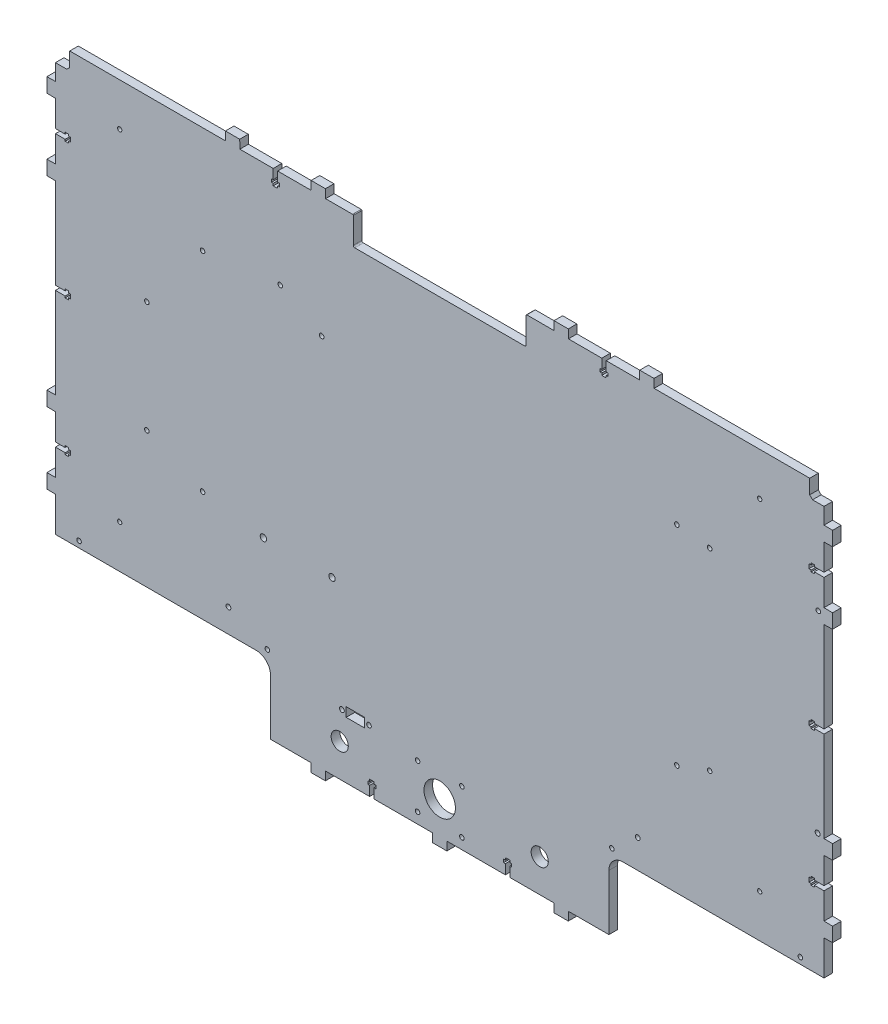
SolidWorks part; units mm, degrees
material "Клен"
ref_plane "Front" through (0, 0, 0) normal (0, 0, 1) x (1, 0, 0)
ref_plane "Top" through (0, 0, 0) normal (0, 1, 0) x (1, 0, 0)
ref_plane "Right" through (0, 0, 0) normal (1, 0, 0) x (0, 0, -1)
sketch "Эскиз1" plane through (0, 0, 0) normal (0, 0, 1) x (1, 0, 0)
  line L0 (89.7419, 500.1376) -> (118.0919, 500.1376)
  line L1 (118.0919, 500.1376) -> (118.1919, 494.1376)
  line L2 (118.1919, 494.1376) -> (128.1919, 494.1376)
  line L3 (128.1919, 494.1376) -> (128.2919, 500.1376)
  line L4 (128.2919, 500.1376) -> (159.1419, 500.1376)
  line L5 (159.1419, 500.1376) -> (159.1419, 506.9376)
  line L6 (159.1419, 506.9376) -> (157.9419, 506.9376)
  line L7 (157.9419, 506.9376) -> (157.9419, 509.1376)
  line L8 (157.9419, 509.1376) -> (159.1419, 509.1376)
  line L9 (159.1419, 509.1376) -> (159.1419, 510.6376)
  line L10 (159.1419, 510.6376) -> (162.2419, 510.6376)
  line L11 (162.2419, 510.6376) -> (162.2419, 509.1376)
  line L12 (162.2419, 509.1376) -> (163.4419, 509.1376)
  line L13 (163.4419, 509.1376) -> (163.4419, 506.9376)
  line L14 (163.4419, 506.9376) -> (162.2419, 506.9376)
  line L15 (162.2419, 506.9376) -> (162.2419, 500.1376)
  line L16 (-51.8081, 695.792) -> (-54.0081, 695.792)
  line L17 (-66.8081, 623.542) -> (-60.8081, 623.442)
  line L18 (162.2419, 500.1376) -> (203.0919, 500.1376)
  line L19 (203.0919, 500.1376) -> (203.1919, 494.1376)
  line L20 (203.1919, 494.1376) -> (213.1919, 494.1376)
  line L21 (213.1919, 494.1376) -> (213.2919, 500.1376)
  line L22 (213.2919, 500.1376) -> (254.1419, 500.1376)
  line L23 (254.1419, 500.1376) -> (254.1419, 506.9376)
  line L24 (254.1419, 506.9376) -> (252.9419, 506.9376)
  line L25 (252.9419, 506.9376) -> (252.9419, 509.1376)
  line L26 (252.9419, 509.1376) -> (254.1419, 509.1376)
  line L27 (254.1419, 509.1376) -> (254.1419, 510.6376)
  line L28 (254.1419, 510.6376) -> (257.2419, 510.6376)
  line L29 (257.2419, 510.6376) -> (257.2419, 509.1376)
  line L30 (257.2419, 509.1376) -> (258.4419, 509.1376)
  line L31 (258.4419, 509.1376) -> (258.4419, 506.9376)
  line L32 (258.4419, 506.9376) -> (257.2419, 506.9376)
  line L33 (257.2419, 506.9376) -> (257.2419, 500.1376)
  line L34 (257.2419, 500.1376) -> (288.0919, 500.1376)
  line L35 (288.0919, 500.1376) -> (288.1919, 494.1376)
  line L36 (288.1919, 494.1376) -> (298.1919, 494.1376)
  line L37 (298.1919, 494.1376) -> (298.2919, 500.1376)
  line L38 (298.2919, 500.1376) -> (326.6419, 500.1376)
  line L97 (367.1919, 847.1376) -> (358.2919, 847.1376)
  line L98 (358.2919, 847.1376) -> (358.1919, 853.1376)
  line L99 (358.1919, 853.1376) -> (348.1919, 853.1376)
  line L100 (348.1919, 853.1376) -> (348.0919, 847.1376)
  line L101 (348.0919, 847.1376) -> (324.7419, 847.1376)
  line L102 (324.7419, 847.1376) -> (324.7419, 840.3376)
  line L103 (324.7419, 840.3376) -> (325.9419, 840.3376)
  line L104 (325.9419, 840.3376) -> (325.9419, 838.1376)
  line L105 (325.9419, 838.1376) -> (324.7419, 838.1376)
  line L106 (324.7419, 838.1376) -> (324.7419, 836.6376)
  line L107 (324.7419, 836.6376) -> (321.6419, 836.6376)
  line L108 (321.6419, 836.6376) -> (321.6419, 838.1376)
  line L109 (321.6419, 838.1376) -> (320.4419, 838.1376)
  line L110 (320.4419, 838.1376) -> (320.4419, 840.3376)
  line L111 (320.4419, 840.3376) -> (321.6419, 840.3376)
  line L112 (321.6419, 840.3376) -> (321.6419, 847.1376)
  line L113 (321.6419, 847.1376) -> (298.2919, 847.1376)
  line L114 (298.2919, 847.1376) -> (298.1919, 853.1376)
  line L115 (298.1919, 853.1376) -> (288.1919, 853.1376)
  line L116 (288.1919, 853.1376) -> (288.0919, 847.1376)
  line L117 (288.0919, 847.1376) -> (269.1919, 847.1376)
  line L118 (268.6919, 846.6376) -> (268.6919, 828.542)
  line L119 (267.6919, 827.542) -> (148.6919, 827.542)
  line L120 (147.6919, 828.542) -> (147.6919, 846.542)
  line L130 (94.7419, 838.042) -> (94.7419, 836.542)
  line L131 (94.7419, 836.542) -> (91.6419, 836.542)
  line L132 (91.6419, 836.542) -> (91.6419, 838.042)
  line L199 (39.1919, 871.432) -> (39.1919, 501.6876) construction
  line L201 (142.7002, 546.3976) -> (155.7002, 546.3976)
  line L202 (155.7002, 546.3976) -> (155.7002, 539.8976)
  line L203 (155.7002, 539.8976) -> (142.7002, 539.8976)
  line L204 (142.7002, 539.8976) -> (142.7002, 546.3976)
  line L205 (-60.8081, 871.432) -> (-60.8081, 501.6876) construction
  line L206 (-50.3081, 791.992) -> (-51.8081, 791.992)
  line L207 (-60.8081, 696.992) -> (-60.8081, 633.642)
  line L208 (-60.8081, 795.092) -> (-54.0081, 795.092)
  line L209 (-51.8081, 791.992) -> (-51.8081, 790.792)
  line L210 (-54.0081, 700.092) -> (-54.0081, 701.292)
  line L211 (-51.8081, 700.092) -> (-50.3081, 700.092)
  line L212 (-60.8081, 835.042) -> (-60.8081, 823.642)
  line L213 (-51.8081, 795.092) -> (-50.3081, 795.092)
  line L214 (-54.0081, 701.292) -> (-51.8081, 701.292)
  line L215 (-50.3081, 696.992) -> (-51.8081, 696.992)
  line L216 (-54.0081, 601.992) -> (-60.8081, 601.992)
  line L217 (-60.8081, 773.642) -> (-66.8081, 773.542)
  line L218 (-50.3081, 601.992) -> (-51.8081, 601.992)
  line L219 (-60.8081, 813.442) -> (-60.8081, 795.092)
  line L220 (-54.0081, 795.092) -> (-54.0081, 796.292)
  line L221 (-54.0081, 796.292) -> (-51.8081, 796.292)
  line L222 (-51.8081, 696.992) -> (-51.8081, 695.792)
  line L223 (-54.0081, 606.292) -> (-51.8081, 606.292)
  line L224 (-60.8081, 573.442) -> (-60.8081, 549.042)
  line L225 (-52.8081, 835.042) -> (-60.8081, 835.042)
  line L226 (-54.0081, 790.792) -> (-54.0081, 791.992)
  line L227 (-51.8081, 605.092) -> (-50.3081, 605.092)
  line L228 (-66.8081, 583.542) -> (-66.8081, 573.542)
  line L229 (-51.8081, 790.792) -> (-54.0081, 790.792)
  line L230 (-54.0081, 605.092) -> (-54.0081, 606.292)
  line L231 (-51.8081, 601.992) -> (-51.8081, 600.792)
  line L232 (-66.8081, 823.542) -> (-66.8081, 813.542)
  line L233 (-50.3081, 795.092) -> (-50.3081, 791.992)
  line L234 (-60.8081, 633.642) -> (-66.8081, 633.542)
  line L235 (-60.8081, 583.642) -> (-66.8081, 583.542)
  line L236 (-66.8081, 813.542) -> (-60.8081, 813.442)
  line L237 (-66.8081, 773.542) -> (-66.8081, 763.542)
  line L238 (-51.8081, 600.792) -> (-54.0081, 600.792)
  line L239 (-66.8081, 763.542) -> (-60.8081, 763.442)
  line L240 (-50.3081, 700.092) -> (-50.3081, 696.992)
  line L241 (-60.8081, 623.442) -> (-60.8081, 605.092)
  line L243 (-54.0081, 791.992) -> (-60.8081, 791.992)
  line L244 (-54.0081, 695.792) -> (-54.0081, 696.992)
  line L245 (-60.8081, 823.642) -> (-66.8081, 823.542)
  line L246 (-51.8081, 796.292) -> (-51.8081, 795.092)
  line L247 (-51.8081, 701.292) -> (-51.8081, 700.092)
  line L248 (-60.8081, 601.992) -> (-60.8081, 583.642)
  line L249 (-54.0081, 696.992) -> (-60.8081, 696.992)
  line L250 (-66.8081, 633.542) -> (-66.8081, 623.542)
  line L251 (-60.8081, 763.442) -> (-60.8081, 700.092)
  line L252 (-54.0081, 600.792) -> (-54.0081, 601.992)
  line L254 (-50.8081, 847.042) -> (-50.8081, 837.042)
  line L255 (-50.8081, 837.042) -> (-52.8081, 835.042)
  line L256 (-60.8081, 700.092) -> (-54.0081, 700.092)
  line L257 (-60.8081, 605.092) -> (-54.0081, 605.092)
  line L258 (-50.3081, 605.092) -> (-50.3081, 601.992)
  line L259 (-60.8081, 791.992) -> (-60.8081, 773.642)
  line L260 (-51.8081, 606.292) -> (-51.8081, 605.092)
  line L261 (-66.8081, 573.542) -> (-60.8081, 573.442)
  line L264 (377.1919, 871.432) -> (377.1919, 476.2445) construction
  line L265 (477.1919, 835.042) -> (477.1919, 823.642)
  line L325 (367.1919, 847.1376) -> (467.1919, 847.1376)
  line L326 (336.6419, 549.1376) -> (377.1919, 549.1376)
  line L327 (326.6419, 500.1376) -> (326.6419, 539.1376)
  line L328 (377.1919, 549.1376) -> (477.1919, 549.1376)
  line L329 (89.7419, 539.042) -> (89.7419, 500.1376)
  line L330 (79.7419, 549.042) -> (39.1919, 549.042)
  line L331 (-60.8081, 549.042) -> (39.1919, 549.042)
  line L332 (208.1919, 486.1481) -> (208.1919, 880.8098) construction
  line L333 (107.749, 553.442) -> (-66.0548, 553.442) construction
  line L334 (315.5919, 553.5376) -> (489.3697, 553.5376) construction
  line L335 (87.5419, 557.9345) -> (87.5419, 540.5243) construction
  line L336 (328.7419, 492.2341) -> (328.7419, 562.4741) construction
  line L337 (42.1919, 871.432) -> (42.1919, 565.6434) construction
  line L338 (-84.499, 772.492) -> (54.9834, 772.492) construction
  line L339 (-84.499, 626.492) -> (54.9834, 626.492) construction
  line L340 (94.7419, 840.3376) -> (94.7419, 847.1376)
  line L341 (95.9419, 840.3376) -> (94.7419, 840.3376)
  line L342 (95.9419, 838.1376) -> (95.9419, 840.3376)
  line L343 (94.7419, 838.1376) -> (95.9419, 838.1376)
  line L344 (94.7419, 836.6376) -> (94.7419, 838.1376)
  line L345 (91.6419, 836.6376) -> (94.7419, 836.6376)
  line L346 (91.6419, 838.1376) -> (91.6419, 836.6376)
  line L347 (90.4419, 838.1376) -> (91.6419, 838.1376)
  line L348 (90.4419, 840.3376) -> (90.4419, 838.1376)
  line L349 (91.6419, 840.3376) -> (90.4419, 840.3376)
  line L350 (91.6419, 847.1376) -> (91.6419, 840.3376)
  line L351 (49.1919, 847.1376) -> (-50.8081, 847.1376)
  line L352 (128.2919, 847.1376) -> (147.1919, 847.1376)
  line L353 (128.1919, 853.1376) -> (128.2919, 847.1376)
  line L354 (118.1919, 853.1376) -> (128.1919, 853.1376)
  line L355 (118.0919, 847.1376) -> (118.1919, 853.1376)
  line L356 (94.7419, 847.1376) -> (118.0919, 847.1376)
  line L357 (68.2919, 847.1376) -> (91.6419, 847.1376)
  line L358 (68.1919, 853.1376) -> (68.2919, 847.1376)
  line L359 (58.1919, 853.1376) -> (68.1919, 853.1376)
  line L360 (58.0919, 847.1376) -> (58.1919, 853.1376)
  line L361 (49.1919, 847.1376) -> (58.0919, 847.1376)
  line L362 (147.6919, 846.6376) -> (147.6919, 846.542)
  line L363 (-50.8081, 847.1376) -> (-50.8081, 847.042)
  line L364 (467.1919, 847.1376) -> (467.1919, 847.042)
  line L365 (467.1919, 837.042) -> (469.1919, 835.042)
  line L366 (467.1919, 847.042) -> (467.1919, 837.042)
  line L367 (469.1919, 835.042) -> (477.1919, 835.042)
  line L368 (477.1919, 791.992) -> (477.1919, 773.642)
  line L369 (468.1919, 796.292) -> (468.1919, 795.092)
  line L370 (477.1919, 823.642) -> (483.1919, 823.542)
  line L371 (470.3919, 791.992) -> (477.1919, 791.992)
  line L372 (483.1919, 813.542) -> (477.1919, 813.442)
  line L373 (466.6919, 795.092) -> (466.6919, 791.992)
  line L374 (483.1919, 823.542) -> (483.1919, 813.542)
  line L375 (468.1919, 790.792) -> (470.3919, 790.792)
  line L376 (470.3919, 790.792) -> (470.3919, 791.992)
  line L377 (470.3919, 796.292) -> (468.1919, 796.292)
  line L378 (470.3919, 795.092) -> (470.3919, 796.292)
  line L379 (477.1919, 813.442) -> (477.1919, 795.092)
  line L380 (468.1919, 795.092) -> (466.6919, 795.092)
  line L381 (468.1919, 791.992) -> (468.1919, 790.792)
  line L382 (477.1919, 795.092) -> (470.3919, 795.092)
  line L383 (466.6919, 791.992) -> (468.1919, 791.992)
  line L384 (483.1919, 763.542) -> (477.1919, 763.442)
  line L385 (483.1919, 773.542) -> (483.1919, 763.542)
  line L386 (477.1919, 773.642) -> (483.1919, 773.542)
  line L387 (477.1919, 763.442) -> (477.1919, 700.092)
  line L388 (477.1919, 700.092) -> (470.3919, 700.092)
  line L389 (470.3919, 696.992) -> (477.1919, 696.992)
  line L390 (468.1919, 701.292) -> (468.1919, 700.092)
  line L391 (470.3919, 695.792) -> (470.3919, 696.992)
  line L392 (466.6919, 700.092) -> (466.6919, 696.992)
  line L393 (468.1919, 696.992) -> (468.1919, 695.792)
  line L394 (466.6919, 696.992) -> (468.1919, 696.992)
  line L395 (470.3919, 701.292) -> (468.1919, 701.292)
  line L396 (468.1919, 700.092) -> (466.6919, 700.092)
  line L397 (470.3919, 700.092) -> (470.3919, 701.292)
  line L398 (468.1919, 695.792) -> (470.3919, 695.792)
  line L399 (477.1919, 696.992) -> (477.1919, 633.642)
  line L400 (477.1919, 601.992) -> (477.1919, 583.642)
  line L401 (468.1919, 606.292) -> (468.1919, 605.092)
  line L402 (466.6919, 605.092) -> (466.6919, 601.992)
  line L403 (477.1919, 605.092) -> (470.3919, 605.092)
  line L404 (470.3919, 600.792) -> (470.3919, 601.992)
  line L405 (483.1919, 633.542) -> (483.1919, 623.542)
  line L406 (477.1919, 623.442) -> (477.1919, 605.092)
  line L407 (468.1919, 600.792) -> (470.3919, 600.792)
  line L408 (477.1919, 633.642) -> (483.1919, 633.542)
  line L409 (468.1919, 601.992) -> (468.1919, 600.792)
  line L410 (470.3919, 605.092) -> (470.3919, 606.292)
  line L411 (468.1919, 605.092) -> (466.6919, 605.092)
  line L412 (470.3919, 606.292) -> (468.1919, 606.292)
  line L413 (466.6919, 601.992) -> (468.1919, 601.992)
  line L414 (470.3919, 601.992) -> (477.1919, 601.992)
  line L415 (483.1919, 623.542) -> (477.1919, 623.442)
  line L416 (483.1919, 573.542) -> (477.1919, 573.442)
  line L417 (477.1919, 583.642) -> (483.1919, 583.542)
  line L418 (483.1919, 583.542) -> (483.1919, 573.542)
  line L419 (477.1919, 573.442) -> (477.1919, 549.042)
  line L420 (432.1919, 871.432) -> (432.1919, 500.1376) construction
  line L421 (460.6419, 817.1376) -> (383.8191, 817.1376) construction
  line L422 (468.1919, 579.1376) -> (402.4026, 579.1376) construction
  circle A0 centre (138.1919, 523.1376) radius 6
  circle A1 centre (208.1919, 523.1376) radius 11
  circle A2 centre (278.1919, 523.1376) radius 6
  circle A3 centre (192.6919, 538.6376) radius 1.6
  circle A4 centre (223.6919, 538.6376) radius 1.6
  circle A5 centre (158.7002, 543.1376) radius 1.6265
  circle A6 centre (139.7002, 543.1376) radius 1.7
  circle A7 centre (192.6919, 507.6376) radius 1.6
  circle A8 centre (223.6919, 507.6376) radius 1.6
  circle A18 centre (84.7857, 619.7888) radius 2.25
  circle A19 centre (132.7857, 619.7888) radius 2.25
  circle A24 centre (346.7847, 569.0716) radius 1.7
  circle A26 centre (60.3069, 565.6434) radius 1.7
  arc A30 (148.6919, 827.542) -> (147.6919, 828.542) centre (148.6919, 828.542) cw
  arc A31 (268.6919, 828.542) -> (267.6919, 827.542) centre (267.6919, 828.542) cw
  arc A32 (269.1919, 847.1376) -> (268.6919, 846.6376) centre (269.1919, 846.6376) ccw
  arc A38 (326.6419, 539.1376) -> (336.6419, 549.1376) centre (336.6419, 539.1376) cw
  arc A39 (89.7419, 539.042) -> (79.7419, 549.042) centre (79.7419, 539.042) ccw
  circle A40 centre (-44.2581, 553.442) radius 1.6
  circle A41 centre (460.6419, 553.5376) radius 1.6
  circle A46 centre (87.5419, 553.442) radius 1.6
  circle A47 centre (328.7419, 553.5376) radius 1.6
  circle A48 centre (42.1919, 772.492) radius 1.6
  circle A49 centre (42.1919, 626.492) radius 1.6
  circle A50 centre (374.1919, 626.492) radius 1.6
  circle A51 centre (374.1919, 772.492) radius 1.6
  circle A52 centre (397.1919, 769.7505) radius 1.6
  circle A53 centre (473.1919, 769.7505) radius 1.6
  circle A55 centre (397.1919, 634.7505) radius 1.6
  arc A56 (147.1919, 847.1376) -> (147.6919, 846.6376) centre (147.1919, 846.6376) cw
  circle A57 centre (96.5604, 778.9111) radius 1.6
  circle A58 centre (125.5604, 762.4937) radius 1.6
  circle A59 centre (3.1919, 722.1376) radius 1.6
  circle A60 centre (3.1919, 644.1376) radius 1.6
  circle A61 centre (432.1919, 817.1376) radius 1.5
  circle A62 centre (432.1919, 579.1376) radius 1.5
  circle A63 centre (-15.8081, 817.1376) radius 1.5
  circle A64 centre (-15.8081, 579.1376) radius 1.5
  circle A65 centre (472.7406, 634.7505) radius 1.75
  dimension "D1" = 12
  dimension "D2" = 22
  dimension "D3" = 12
  dimension "D4" = 169
  dimension "D5" = 1
  dimension "D6" = 0.5
  dimension "D10" = 3.2
  dimension "D12" = 3.2
  dimension "D13" = 4.4
  dimension "D14" = 48.35
  dimension "D15" = 3.2
  dimension "D17" = 3.2
  dimension "D21" = 3.2
  dimension "D22" = 3.2
  dimension "D24" = 23
  dimension "D26" = 31
  dimension "D27" = 31
  dimension "D28" = 31
  dimension "D30" = 23
  dimension "D32" = 43
  dimension "D33" = 43
  dimension "D34" = 3.2
  dimension "D35" = 3.2
  dimension "D36" = 3.2
  dimension "D37" = 3.2
  dimension "D19" = 3.2
  dimension "D38" = 3.2
  dimension "D39" = 3.2
  dimension "D40" = 48
  dimension "D44" = 3
  dimension "D45" = 3
  dimension "D7" = 100
  dimension "D8" = 4.4
  dimension "D9" = 169
  dimension "D11" = 16.55
  dimension "D16" = 48.45
  dimension "D18" = 3
  dimension "D20" = 146
  dimension "D23" = 23
  dimension "D25" = 7.5
  dimension "D29" = 7.5
  dimension "D31" = 39.76
  dimension "D41" = 55
  dimension "D42" = 30
  dimension "D43" = 30
extrude "Бобышка-Вытянуть1" add sketch "Эскиз1" along normal blind 6 contours L0 L1 L2 L3 L4 L5 L6 L7 L8 L9 L10 L11 L12 L13 L14 L15 L18 L19 L20 L21 L22 L23 L24 L25 L26 L27 L28 L29 L30 L31 L32 L33 L34 L35 L36 L37 L38 region at (208.2136, 684.8413, 0)
